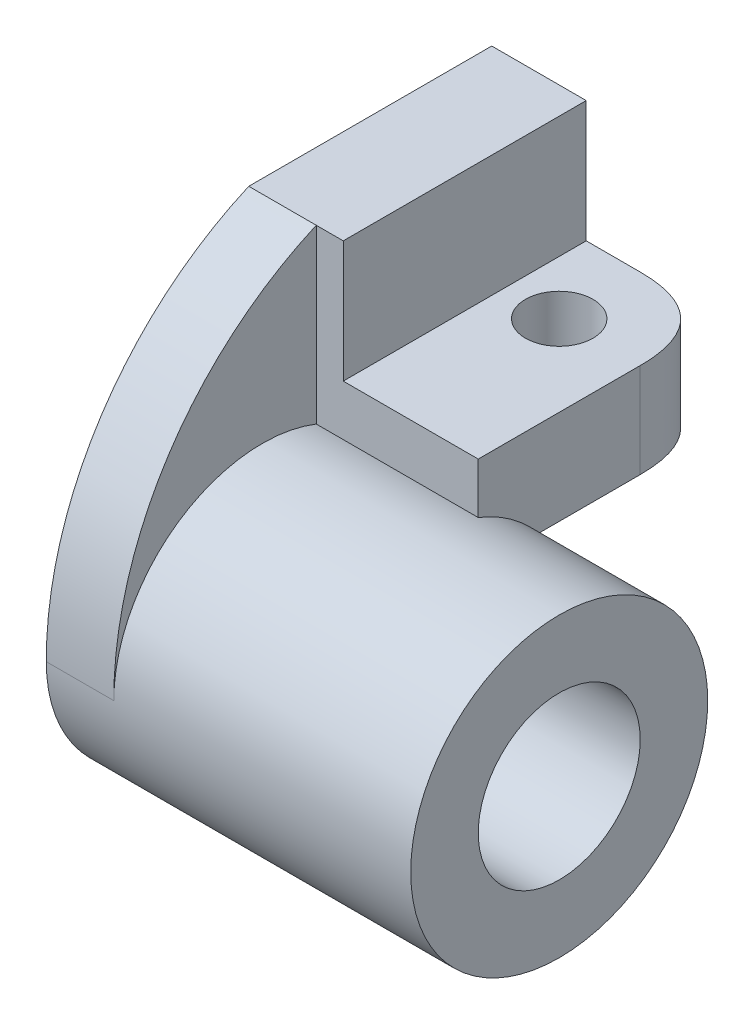
SolidWorks part; units mm, degrees
note: The reader was unsure of these and kept them because the rebuilt part matched: shared geometry of "Sketch1<3>", "Sketch1<4>", "Sketch1<5>".
ref_plane "Front Plane" through (0, 0, 0) normal (0, 0, 1) x (1, 0, 0)
ref_plane "Top Plane" through (0, 0, 0) normal (0, 1, 0) x (1, 0, 0)
ref_plane "Right Plane" through (0, 0, 0) normal (1, 0, 0) x (0, 0, -1)
sketch "Sketch1" plane through (0, 0, 0) normal (1, 0, 0) x (0, 0, -1)
  line L0 (12.7, 44.45) -> (69.85, 44.45)
  line L1 (69.85, 44.45) -> (69.85, 22.225)
  line L2 (69.85, 22.225) -> (26.9408, 22.225)
  line L3 (12.7, 44.45) -> (12.7, 73.025)
  line L4 (12.7, 73.025) -> (69.85, 73.025)
  line L5 (69.85, 73.025) -> (69.85, 44.45)
  line L6 (12.7, 44.45) -> (12.7, 32.5341)
  circle A0 centre (0, 0) radius 34.925
  circle A1 centre (0, 0) radius 19.05
  arc A2 (-34.925, 0) -> (12.7, 73.025) centre (44.4495, 0.2764) cw
  dimension "D1" = 69.85
  dimension "D2" = 38.1
  dimension "D6" = 79.375
  dimension "D3" = 44.45
  dimension "D4" = 57.15
  dimension "D5" = 22.225
  dimension "D7" = 28.575
  dimension "D8" = 69.85
extrude "Boss-Extrude1" add sketch "Sketch1" along normal blind 85.725 contours A0 A1
extrude "Boss-Extrude2" add sketch "Sketch1<3>" along normal blind 53.975 contours A0 L2 L1 L0 L6
sketch "Sketch1<3>" plane through (0, 0, 0) normal (1, 0, 0) x (0, 0, -1) same geometry as "Sketch1"
extrude "Boss-Extrude3" add sketch "Sketch1<4>" along normal blind 22.225 contours L5 L4 L3 L0
sketch "Sketch1<4>" plane through (0, 0, 0) normal (1, 0, 0) x (0, 0, -1) same geometry as "Sketch1"
extrude "Boss-Extrude4" add sketch "Sketch1<5>" along normal blind 15.875 contours A2 A0 L6 L3
sketch "Sketch1<5>" plane through (0, 0, 0) normal (1, 0, 0) x (0, 0, -1) same geometry as "Sketch1"
fillet "Fillet1" radius 19.05 1 edges at (53.975, 33.3375, -69.85)
sketch "Sketch2" plane through (0, 44.45, 0) normal (0, 1, 0) x (1, 0, 0)
  line L0 (53.975, 12.7) -> (53.975, 50.8) construction
  line L1 (34.925, 69.85) -> (22.225, 69.85) construction
  circle A0 centre (34.925, 50.8) radius 7.9375
  dimension "D1" = 15.875
  dimension "D2" = 19.05
  dimension "D3" = 19.05
extrude "Cut-Extrude1" cut sketch "Sketch2" against normal through all
